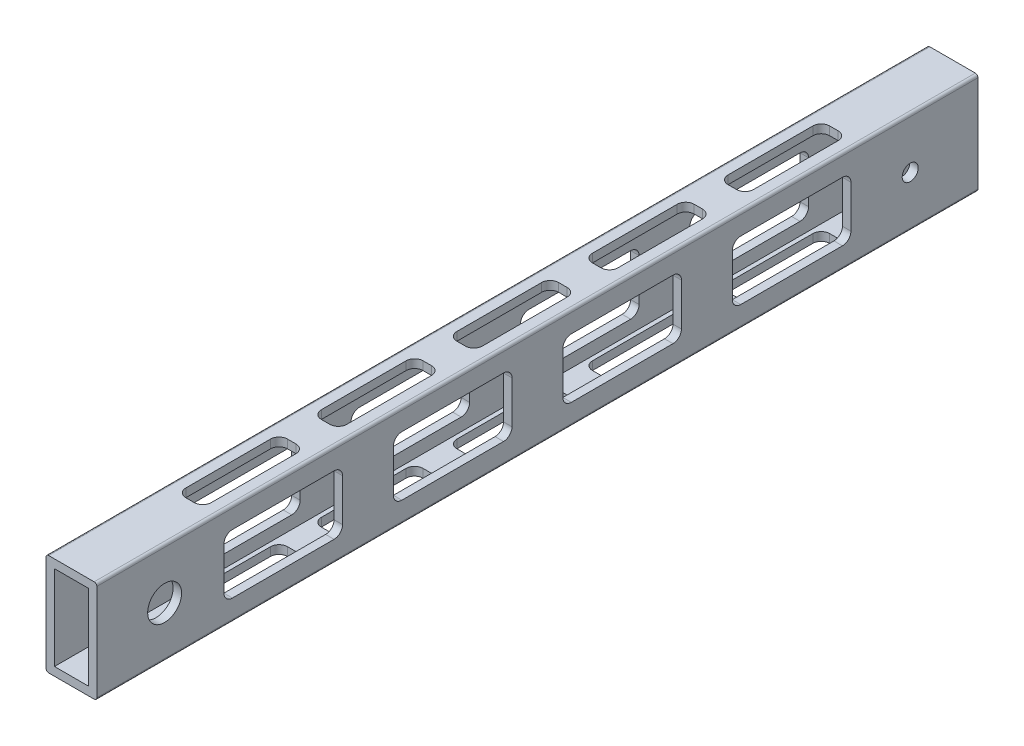
SolidWorks part; units mm, degrees
material "6061-T6 (SS)"
ref_plane "Front Plane" through (0, 0, 0) normal (0, 0, 1) x (1, 0, 0)
ref_plane "Top Plane" through (0, 0, 0) normal (0, 1, 0) x (1, 0, 0)
ref_plane "Right Plane" through (0, 0, 0) normal (1, 0, 0) x (0, 0, -1)
sketch "Sketch1" plane through (0, 0, 0) normal (0, 0, 1) x (1, 0, 0)
  line L0 (-6.35, -15.875) -> (-6.35, 15.875)
  line L1 (-8.525, -19.05) -> (8.525, -19.05)
  line L2 (-9.525, -18.05) -> (-9.525, 18.05)
  line L3 (-8.525, 19.05) -> (8.525, 19.05)
  line L4 (9.525, -18.05) -> (9.525, 18.05)
  line L5 (-9.525, -19.05) -> (9.525, 19.05) construction
  line L6 (-9.525, 19.05) -> (9.525, -19.05) construction
  line L7 (-6.35, 15.875) -> (6.35, 15.875)
  line L8 (6.35, -15.875) -> (6.35, 15.875)
  line L9 (-6.35, -15.875) -> (6.35, -15.875)
  arc A0 (-8.525, -19.05) -> (-9.525, -18.05) centre (-8.525, -18.05) cw
  arc A1 (8.525, -19.05) -> (9.525, -18.05) centre (8.525, -18.05) ccw
  arc A2 (8.525, 19.05) -> (9.525, 18.05) centre (8.525, 18.05) cw
  arc A3 (-9.525, 18.05) -> (-8.525, 19.05) centre (-8.525, 18.05) cw
  arc A4 (-6.35, 15.875) -> (-6.35, 15.875) centre (-6.35, 15.875) cw
  arc A5 (6.35, 15.875) -> (6.35, 15.875) centre (6.35, 15.875) cw
  arc A6 (6.35, -15.875) -> (6.35, -15.875) centre (6.35, -15.875) ccw
  arc A7 (-6.35, -15.875) -> (-6.35, -15.875) centre (-6.35, -15.875) cw
  point P0 (0, 0)
  dimension "D3" = 1
  dimension "D1" = 19.05
  dimension "D2" = 38.1
  dimension "D4" = 3.175
extrude "Boss-Extrude1" add sketch "Sketch1" along normal mid plane 330.2
sketch "Sketch2" plane through (0, 19.05, 0) normal (0, 1, 0) x (1, 0, 0)
  line L0 (-4.7625, -66.675) -> (-4.7625, -34.925)
  line L1 (-1.5875, -120.65) -> (1.5875, -120.65)
  line L2 (-4.7625, -117.475) -> (-4.7625, -85.725)
  line L3 (-1.5875, -82.55) -> (1.5875, -82.55)
  line L4 (4.7625, -117.475) -> (4.7625, -85.725)
  line L5 (-4.7625, -120.65) -> (4.7625, -82.55) construction
  line L6 (-4.7625, -82.55) -> (4.7625, -120.65) construction
  line L7 (-1.5875, -69.85) -> (1.5875, -69.85)
  line L8 (4.7625, -66.675) -> (4.7625, -34.925)
  line L9 (-1.5875, -31.75) -> (1.5875, -31.75)
  line L10 (-4.7625, -15.875) -> (-4.7625, 15.875)
  line L11 (-1.5875, -19.05) -> (1.5875, -19.05)
  line L12 (4.7625, -15.875) -> (4.7625, 15.875)
  line L13 (-1.5875, 19.05) -> (1.5875, 19.05)
  line L14 (-4.7625, 34.925) -> (-4.7625, 66.675)
  line L15 (-1.5875, 31.75) -> (1.5875, 31.75)
  line L16 (4.7625, 34.925) -> (4.7625, 66.675)
  line L17 (-1.5875, 69.85) -> (1.5875, 69.85)
  line L18 (-4.7625, 85.725) -> (-4.7625, 117.475)
  line L19 (-1.5875, 82.55) -> (1.5875, 82.55)
  line L20 (4.7625, 85.725) -> (4.7625, 117.475)
  line L21 (-1.5875, 120.65) -> (1.5875, 120.65)
  line L22 (0, -101.6) -> (0, -50.8) construction
  arc A0 (-1.5875, -120.65) -> (-4.7625, -117.475) centre (-1.5875, -117.475) cw
  arc A1 (1.5875, -120.65) -> (4.7625, -117.475) centre (1.5875, -117.475) ccw
  arc A2 (1.5875, -82.55) -> (4.7625, -85.725) centre (1.5875, -85.725) cw
  arc A3 (-4.7625, -85.725) -> (-1.5875, -82.55) centre (-1.5875, -85.725) cw
  arc A4 (-4.7625, -34.925) -> (-1.5875, -31.75) centre (-1.5875, -34.925) cw
  arc A5 (-1.5875, -69.85) -> (-4.7625, -66.675) centre (-1.5875, -66.675) cw
  arc A6 (1.5875, -69.85) -> (4.7625, -66.675) centre (1.5875, -66.675) ccw
  arc A7 (1.5875, -31.75) -> (4.7625, -34.925) centre (1.5875, -34.925) cw
  arc A8 (-4.7625, 15.875) -> (-1.5875, 19.05) centre (-1.5875, 15.875) cw
  arc A9 (-1.5875, -19.05) -> (-4.7625, -15.875) centre (-1.5875, -15.875) cw
  arc A10 (1.5875, -19.05) -> (4.7625, -15.875) centre (1.5875, -15.875) ccw
  arc A11 (1.5875, 19.05) -> (4.7625, 15.875) centre (1.5875, 15.875) cw
  arc A12 (-4.7625, 66.675) -> (-1.5875, 69.85) centre (-1.5875, 66.675) cw
  arc A13 (-1.5875, 31.75) -> (-4.7625, 34.925) centre (-1.5875, 34.925) cw
  arc A14 (1.5875, 31.75) -> (4.7625, 34.925) centre (1.5875, 34.925) ccw
  arc A15 (1.5875, 69.85) -> (4.7625, 66.675) centre (1.5875, 66.675) cw
  arc A16 (-4.7625, 117.475) -> (-1.5875, 120.65) centre (-1.5875, 117.475) cw
  arc A17 (-1.5875, 82.55) -> (-4.7625, 85.725) centre (-1.5875, 85.725) cw
  arc A18 (1.5875, 82.55) -> (4.7625, 85.725) centre (1.5875, 85.725) ccw
  arc A19 (1.5875, 120.65) -> (4.7625, 117.475) centre (1.5875, 117.475) cw
  point P0 (0, -101.6)
  point P5 (0, 0)
  point P19 (0, 0)
  point P20 (0, -50.8)
  point P33 (0, 0)
  point P46 (0, 50.8)
  point P59 (0, 101.6)
  dimension "D3" = 3.175
  dimension "D1" = 9.525
  dimension "D2" = 38.1
  dimension "D5" = 50.8
  dimension "D4" = 5
extrude "Cut-Extrude1" cut sketch "Sketch2" against normal through all both and the other way through all
sketch "Sketch3" plane through (9.525, 0, 0) normal (1, 0, 0) x (0, 0, -1)
  line L0 (-53.975, -7.9375) -> (-53.975, 7.9375)
  line L1 (-114.3, -11.1125) -> (-76.2, -11.1125)
  line L2 (-117.475, -7.9375) -> (-117.475, 7.9375)
  line L3 (-114.3, 11.1125) -> (-76.2, 11.1125)
  line L4 (-73.025, -7.9375) -> (-73.025, 7.9375)
  line L5 (-117.475, -11.1125) -> (-73.025, 11.1125) construction
  line L6 (-117.475, 11.1125) -> (-73.025, -11.1125) construction
  line L7 (-50.8, -11.1125) -> (-12.7, -11.1125)
  line L8 (-9.525, -7.9375) -> (-9.525, 7.9375)
  line L9 (-50.8, 11.1125) -> (-12.7, 11.1125)
  line L10 (9.525, -7.9375) -> (9.525, 7.9375)
  line L11 (12.7, -11.1125) -> (50.8, -11.1125)
  line L12 (53.975, -7.9375) -> (53.975, 7.9375)
  line L13 (12.7, 11.1125) -> (50.8, 11.1125)
  line L14 (-95.25, 0) -> (-31.75, 0) construction
  line L15 (73.025, -7.9375) -> (73.025, 7.9375)
  line L16 (76.2, -11.1125) -> (114.3, -11.1125)
  line L17 (117.475, -7.9375) -> (117.475, 7.9375)
  line L18 (76.2, 11.1125) -> (114.3, 11.1125)
  line L19 (31.75, 0) -> (95.25, 0) construction
  line L28 (-31.75, 0) -> (31.75, 0) construction
  arc A0 (-114.3, -11.1125) -> (-117.475, -7.9375) centre (-114.3, -7.9375) cw
  arc A1 (-76.2, -11.1125) -> (-73.025, -7.9375) centre (-76.2, -7.9375) ccw
  arc A2 (-76.2, 11.1125) -> (-73.025, 7.9375) centre (-76.2, 7.9375) cw
  arc A3 (-117.475, 7.9375) -> (-114.3, 11.1125) centre (-114.3, 7.9375) cw
  arc A4 (-53.975, 7.9375) -> (-50.8, 11.1125) centre (-50.8, 7.9375) cw
  arc A5 (-50.8, -11.1125) -> (-53.975, -7.9375) centre (-50.8, -7.9375) cw
  arc A6 (-12.7, -11.1125) -> (-9.525, -7.9375) centre (-12.7, -7.9375) ccw
  arc A7 (-12.7, 11.1125) -> (-9.525, 7.9375) centre (-12.7, 7.9375) cw
  arc A8 (9.525, 7.9375) -> (12.7, 11.1125) centre (12.7, 7.9375) cw
  arc A9 (12.7, -11.1125) -> (9.525, -7.9375) centre (12.7, -7.9375) cw
  arc A10 (50.8, -11.1125) -> (53.975, -7.9375) centre (50.8, -7.9375) ccw
  arc A11 (50.8, 11.1125) -> (53.975, 7.9375) centre (50.8, 7.9375) cw
  arc A12 (73.025, 7.9375) -> (76.2, 11.1125) centre (76.2, 7.9375) cw
  arc A13 (76.2, -11.1125) -> (73.025, -7.9375) centre (76.2, -7.9375) cw
  arc A14 (114.3, -11.1125) -> (117.475, -7.9375) centre (114.3, -7.9375) ccw
  arc A15 (114.3, 11.1125) -> (117.475, 7.9375) centre (114.3, 7.9375) cw
  point P0 (-95.25, 0)
  point P19 (95.25, 0)
  point P20 (-31.75, 0)
  point P33 (31.75, 0)
  point P60 (0, 0)
  dimension "D3" = 3.175
  dimension "D1" = 22.225
  dimension "D2" = 44.45
  dimension "D5" = 63.5
  dimension "D4" = 4
extrude "Cut-Extrude2" cut sketch "Sketch3" against normal through all both and the other way through all
sketch "Sketch4" plane through (9.525, 0, 0) normal (1, 0, 0) x (0, 0, -1)
  line L0 (-165.1, -18.05) -> (-165.1, 18.05) construction
  line L2 (-139.7, 0) -> (-165.1, 0) construction
  line L3 (-139.7, 0) -> (-139.7, 19.05) construction
  line L4 (165.1, 0) -> (139.7, 0) construction
  line L5 (165.1, -18.05) -> (165.1, 18.05) construction
  line L6 (139.7, 0) -> (139.7, 19.05) construction
  line L7 (-165.1, 19.05) -> (165.1, 19.05) construction
  circle A0 centre (-139.7, 0) radius 6.35
  circle A1 centre (139.7, 0) radius 3
  point P10 (0, 0)
  point P15 (139.7, 0)
  dimension "D1" = 12.7
  dimension "D4" = 6
  dimension "D2" = 19.05
  dimension "D3" = 25.4
extrude "Cut-Extrude3" cut sketch "Sketch4" against normal through all both and the other way through all
